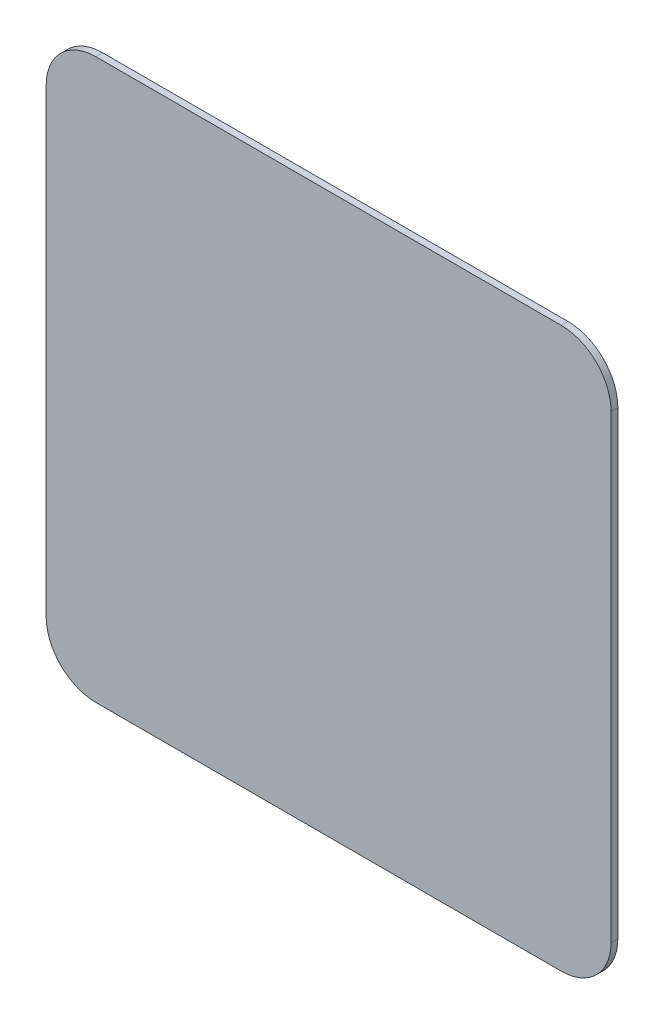
SolidWorks part; units mm, degrees
material "Pine"
ref_plane "Front Plane" through (0, 0, 0) normal (0, 0, 1) x (1, 0, 0)
ref_plane "Top Plane" through (0, 0, 0) normal (0, 1, 0) x (1, 0, 0)
ref_plane "Right Plane" through (0, 0, 0) normal (1, 0, 0) x (0, 0, -1)
sketch "Sketch1" plane through (0, 0, 0) normal (0, 0, 1) x (1, 0, 0)
  line L1 (0, 0) -> (500, 0)
  line L2 (0, 0) -> (0, 495)
  line L3 (0, 495) -> (500, 495)
  line L4 (500, 0) -> (500, 495)
  dimension "D1" = 500
  dimension "D2" = 495
extrude "Boss-Extrude1" add sketch "Sketch1" along normal blind 6
fillet "Fillet1" radius 44 4 edges at (0, 0, 3) (0, 495, 3) (500, 0, 3) (500, 495, 3)
